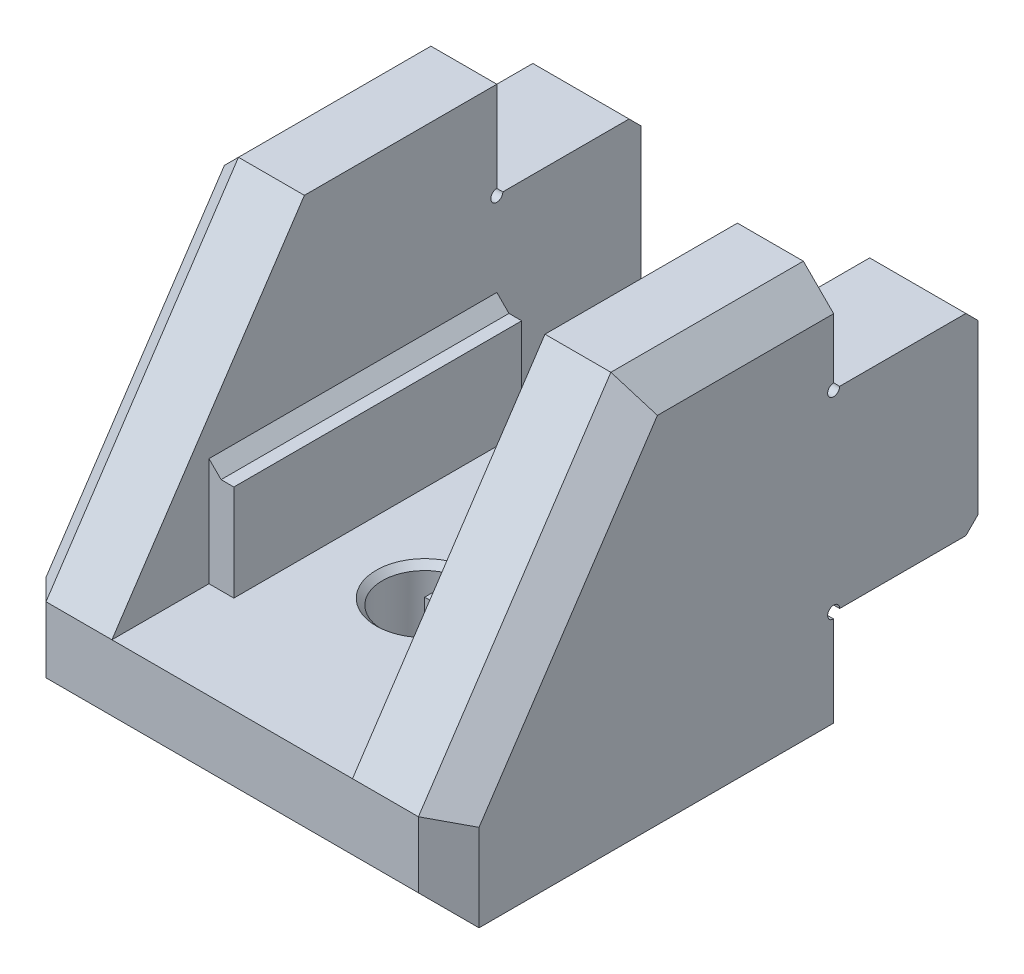
SolidWorks part; units mm, degrees
ref_plane "Front Plane" through (0, 0, 0) normal (0, 0, 1) x (1, 0, 0)
ref_plane "Top Plane" through (0, 0, 0) normal (0, 1, 0) x (1, 0, 0)
ref_plane "Right Plane" through (0, 0, 0) normal (1, 0, 0) x (0, 0, -1)
sketch "Sketch1" plane through (0, 0, 0) normal (0, 1, 0) x (1, 0, 0)
  line L0 (0, 6.35) -> (0, -6.35) construction
  line L1 (7.1437, -6.35) -> (-7.1437, -6.35)
  line L2 (7.1437, -6.35) -> (7.1437, 6.35)
  line L3 (7.1437, 6.35) -> (-7.1437, 6.35)
  line L4 (-7.1437, -6.35) -> (-7.1437, 6.35)
  line L5 (7.1437, -6.35) -> (-7.1437, 6.35) construction
  line L6 (7.1437, 6.35) -> (-7.1437, -6.35) construction
  line L7 (-7.1437, 6.35) -> (-3.9688, 6.35)
  line L8 (-7.1437, 6.35) -> (-7.1437, -6.35)
  line L9 (-7.1437, -6.35) -> (-3.9687, -6.35)
  line L10 (-3.9688, 6.35) -> (-3.9687, -6.35)
  line L11 (7.1437, -6.35) -> (7.1437, 6.35)
  line L12 (3.9688, 6.35) -> (3.9688, -6.35)
  point P0 (0, 0)
  point P10 (3.9688, 6.35)
  point P11 (3.9688, -6.35)
  dimension "D1" = 14.2875
  dimension "D2" = 12.7
  dimension "D3" = 3.175
extrude "Boss-Extrude1" add sketch "Sketch1" along normal blind 3.175 contours L12 L3 L10 L1 region at (0, 0, 0)
extrude "Boss-Extrude2" add sketch "Sketch1<3>" along normal blind 12.7 contours L3 L12 L1 L2 | L10 L3 L4 L1 region at (5.5563, 0, 0) region at (-5.5562, 0, 0)
sketch "Sketch1<3>" plane through (0, 0, 0) normal (0, 1, 0) x (1, 0, 0) same geometry as "Sketch1"
sketch "Sketch2" plane through (7.1437, 0, 0) normal (1, 0, 0) x (0, 0, -1)
  line L1 (-6.35, 3.175) -> (0, 12.7)
  line L2 (-6.35, 12.7) -> (6.35, 12.7) construction
  line L4 (0, 12.7) -> (-6.35, 12.7)
  line L5 (-6.35, 12.7) -> (-6.35, 3.175)
  dimension "D1" = 6.35
extrude "Cut-Extrude2" cut sketch "Sketch2" against normal through all
sketch "Sketch3" plane through (0, 3.175, 0) normal (0, 1, 0) x (1, 0, 0)
  line L0 (3.9688, 6.35) -> (-3.9688, 6.35) construction
  line L2 (3.148, -3.148) -> (3.148, 3.148)
  line L4 (-3.148, -3.148) -> (-3.148, 3.148)
  line L5 (3.148, -3.148) -> (-3.148, 3.148) construction
  line L6 (3.148, 3.148) -> (-3.148, -3.148) construction
  line L7 (-3.148, 6.35) -> (-3.9687, 6.35)
  line L8 (-3.148, 6.35) -> (-3.148, -3.148)
  line L9 (-3.148, -3.148) -> (-3.9687, -3.148)
  line L10 (-3.9687, 6.35) -> (-3.9687, -3.148)
  line L11 (-3.9688, 6.35) -> (-3.9687, -6.35) construction
  line L12 (3.9688, 6.35) -> (3.9688, -6.35) construction
  line L13 (3.148, 6.35) -> (3.9688, 6.35)
  line L14 (3.148, 6.35) -> (3.148, -3.148)
  line L15 (3.148, -3.148) -> (3.9688, -3.148)
  line L16 (3.9688, 6.35) -> (3.9688, -3.148)
  point P0 (0, 0)
  line M3 (3.9688, -6.35) -> (3.9688, 6.35)
  line M4 (3.9688, 6.35) -> (-3.9688, 6.35)
  line M5 (-3.9688, 6.35) -> (-3.9687, -6.35)
  dimension "D1" = 6.296
  dimension "D2" = 6.296
extrude "Boss-Extrude3" add sketch "Sketch3" along normal blind 3.175 contours L9 L4 L8 M4 M5 | L2 L15 L14 M3 M4 region at (-3.5584, 3.175, -1.601) region at (3.5584, 3.175, -1.601)
sketch "Sketch4" plane through (0, 0, -6.35) normal (0, 0, -1) x (-1, 0, 0)
  line L0 (-7.1437, 12.7) -> (-7.1437, 0) construction
  line L1 (-7.1437, 9.525) -> (-3.9688, 9.525)
  line L2 (-7.1437, 9.525) -> (-7.1437, 3.175)
  line L3 (-7.1437, 3.175) -> (-3.9687, 3.175)
  line L4 (-3.9688, 9.525) -> (-3.9687, 3.175)
  line L5 (-7.1437, 12.7) -> (-3.9688, 12.7) construction
  line L6 (0, 3.175) -> (0, 0) construction
  line L7 (-3.148, 3.175) -> (3.148, 3.175) construction
  line L8 (3.9688, 9.525) -> (3.9688, 3.175)
  line L9 (7.1438, 3.175) -> (3.9688, 3.175)
  line L10 (7.1438, 9.525) -> (7.1438, 3.175)
  line L11 (7.1438, 9.525) -> (3.9688, 9.525)
  dimension "D1" = 3.175
  dimension "D2" = 6.35
  dimension "D3" = 3.175
extrude "Boss-Extrude4" add sketch "Sketch4" along normal blind 4.7625
sketch "Sketch5" plane through (7.1437, 0, 0) normal (1, 0, 0) x (0, 0, -1)
  circle A0 centre (6.35, 9.525) radius 0.1984
  circle A1 centre (6.35, 3.175) radius 0.1984
  dimension "D1" = 0.3969
  dimension "D2" = 0.3969
extrude "Cut-Extrude3" cut sketch "Sketch5" against normal through all
chamfer "Chamfer1" distance 0.4 angle 45 6 edges at (-5.5563, 9.525, -11.1125) (-5.5563, 3.175, -11.1125) (5.5562, 3.175, -11.1125) (5.5563, 9.525, -11.1125) (-3.9688, 6.35, -1.601)
chamfer "Chamfer2" distance 1 angle 45 7 edges at (-7.1437, 12.7, -3.175) (7.1437, 12.7, -3.175) (7.1437, 7.9375, 3.175) (-7.1437, 7.9375, 3.175) (-7.1437, 1.5875, 6.35) (7.1437, 1.5875, 6.35) (0, 0, 6.35)
hole_wizard "#35 (0.11) Diameter Hole1" positions "Sketch7" profile "Sketch6" hole size "#35" standard "ANSI Inch" end condition through all
sketch "Sketch7" plane through (0, 3.175, 0) normal (0, 1, 0) x (1, 0, 0)
  point P0 (0, 0)
sketch "Sketch6" plane through (0, 3.175, 0) normal (1, 0, 0) x (0, 0, 1)
  line L0 (0, 0) -> (0, 3.175)
  line L1 (0, 3.175) -> (1.397, 3.175)
  line L2 (1.397, 3.175) -> (1.397, 0)
  line L5 (1.397, 0) -> (0, 0)
  line L11 (0, -6.35) -> (0, 107.95) construction
  dimension "Thru Hole Dia." = 2.794
  dimension "Thru Hole Depth" = 3.175
chamfer "Chamfer3" distance 0.2 angle 45 2 edges at (0, 0, 1.397) (0, 3.175, 1.397)
